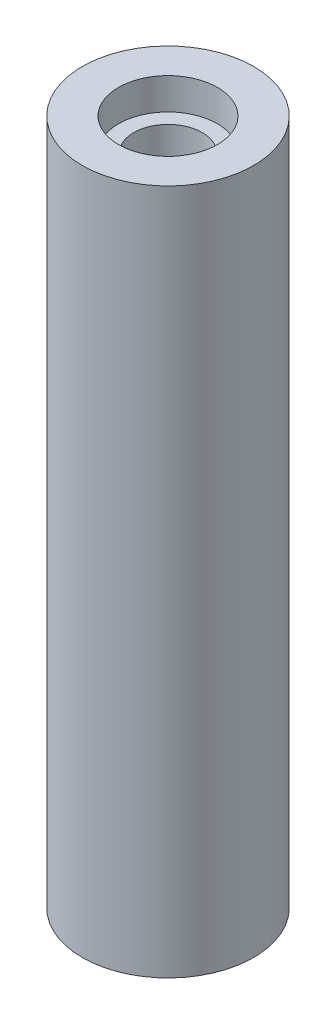
SolidWorks part; units mm, degrees
ref_plane "Front Plane" through (0, 0, 0) normal (0, 0, 1) x (1, 0, 0)
ref_plane "Top Plane" through (0, 0, 0) normal (0, 1, 0) x (1, 0, 0)
ref_plane "Right Plane" through (0, 0, 0) normal (1, 0, 0) x (0, 0, -1)
sketch "Sketch1" plane through (0, 0, 0) normal (0, 1, 0) x (1, 0, 0)
  circle A0 centre (0, 0) radius 19.05
  circle A1 centre (0, 0) radius 7.62
  dimension "D1" = 38.1
  dimension "D2" = 15.24
extrude "Boss-Extrude1" add sketch "Sketch1" along normal blind 152.4
sketch "Sketch3" plane through (0, 152.4, 0) normal (0, 1, 0) x (1, 0, 0)
  circle A0 centre (0, 0) radius 11
  dimension "D1" = 22
extrude "Cut-Extrude2" cut sketch "Sketch3" against normal blind 7
sketch "Sketch4" plane through (0, 0, 0) normal (0, -1, 0) x (1, 0, 0)
  circle A0 centre (0, 0) radius 11
  dimension "D1" = 22
extrude "Cut-Extrude3" cut sketch "Sketch4" against normal blind 7
